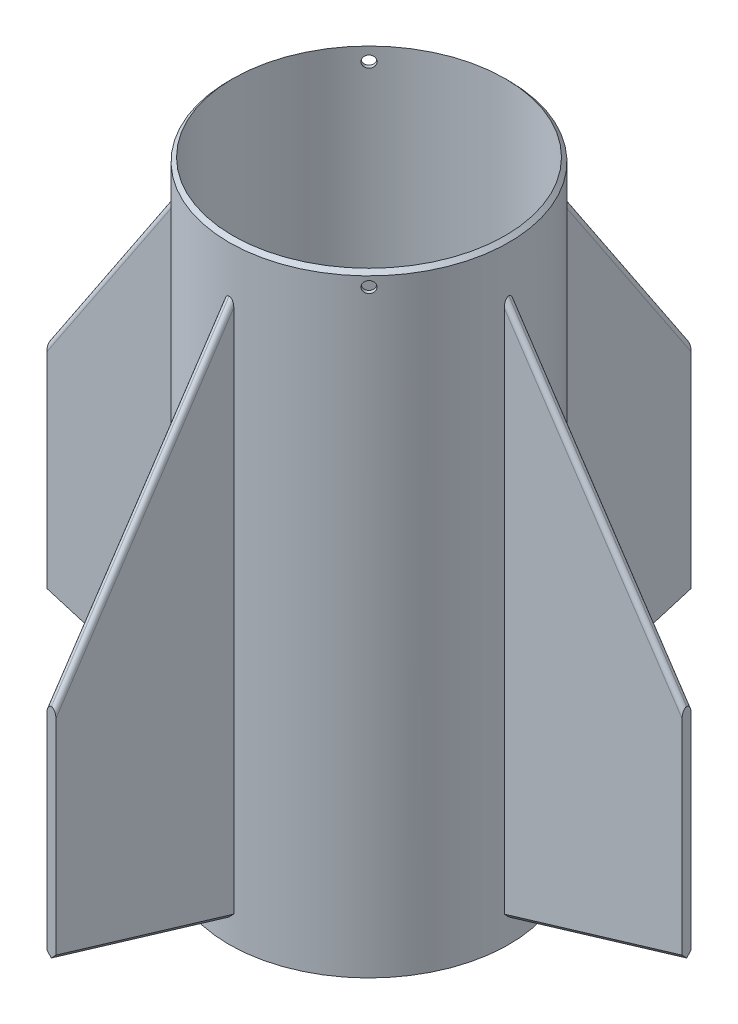
SolidWorks part; units mm, degrees
ref_plane "Front Plane" through (0, 0, 0) normal (0, 0, 1) x (1, 0, 0)
ref_plane "Top Plane" through (0, 0, 0) normal (0, 1, 0) x (1, 0, 0)
ref_plane "Right Plane" through (0, 0, 0) normal (1, 0, 0) x (0, 0, -1)
sketch "Sketch1" plane through (0, 0, 0) normal (0, 1, 0) x (1, 0, 0)
  circle A0 centre (0, 0) radius 76.2
  circle A1 centre (0, 0) radius 78.359
  dimension "D1" = 152.4
  dimension "D2" = 156.718
extrude "Boss-Extrude1" add sketch "Sketch1" along normal blind 342.9
sketch "Sketch2" plane through (0, 0, 0) normal (0, 0, 1) x (1, 0, 0)
  line L0 (76.2, 317.5) -> (76.2, 12.7)
  line L1 (76.2, 12.7) -> (177.8, 43.18)
  line L2 (177.8, 43.18) -> (177.8, 165.1)
  line L3 (177.8, 165.1) -> (76.2, 317.5)
  dimension "D1" = 76.2
  dimension "D2" = 121.92
  dimension "D3" = 101.6
  dimension "D4" = 304.8
  dimension "D5" = 152.4
  dimension "D6" = 12.7
extrude "Boss-Extrude2" add sketch "Sketch2" along normal blind 2.54 and the other way blind 2.54 separate body
sketch "Sketch3" plane through (0, 0, 0) normal (0, 0, 1) x (1, 0, 0)
  line L0 (0, -69.284) -> (0, 493.4849) construction
fillet "Fillet2" radius 2.54 2 edges at (127, 241.3, -2.54) (127, 241.3, 2.54)
chamfer "Chamfer2" distance 2.54 angle 45 2 edges at (127, 27.94, -2.54) (127, 27.94, 2.54)
pattern_circular "CirPattern1" count 4 over 360 about axis through (0, -69.284, 0) along (0, 1, 0) of bodies 102
ref_plane "Plane1" through (0, 0, 0) normal (-0.7071, 0, -0.7071) x (-0.7071, 0, 0.7071)
sketch "Sketch4" plane through (0, 0, 0) normal (-0.7071, 0, -0.7071) x (-0.7071, 0, 0.7071)
  line L0 (0, 342.9) -> (0, 0) construction
  circle A0 centre (0, 334.9498) radius 3.175
  dimension "D1" = 6.35
  dimension "D2" = 334.9498
extrude "Cut-Extrude1" cut sketch "Sketch4" against normal through all contours A0
pattern_circular "CirPattern2" count 4 over 360 about axis through (0, -69.284, 0) along (0, 1, 0) of "Cut-Extrude1" reverse direction yes
chamfer "Chamfer3" distance 2.54 angle 45 1 edges at (0, 342.9, 78.359)
